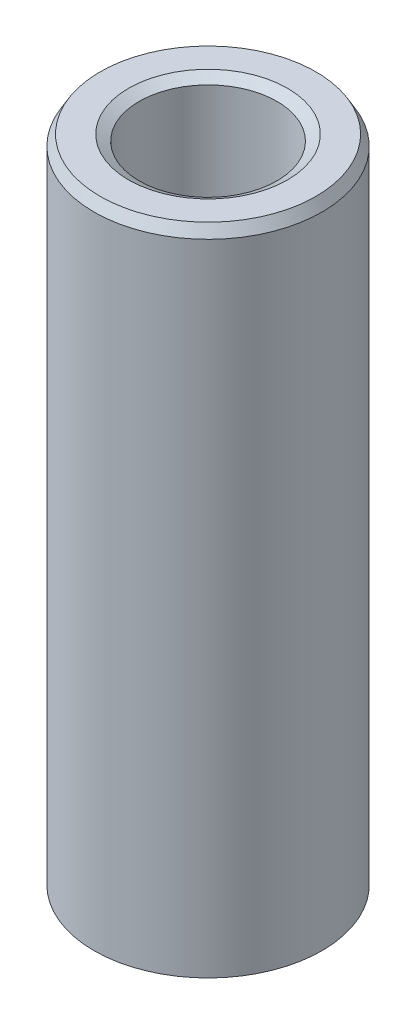
SolidWorks part; units mm, degrees
ref_plane "Front Plane" through (0, 0, 0) normal (0, 0, 1) x (1, 0, 0)
ref_plane "Top Plane" through (0, 0, 0) normal (0, 1, 0) x (1, 0, 0)
ref_plane "Right Plane" through (0, 0, 0) normal (1, 0, 0) x (0, 0, -1)
sketch "Sketch1" plane through (0, 0, 0) normal (0, 1, 0) x (1, 0, 0)
  circle A0 centre (0, 0) radius 15
  dimension "SLEEVE_OD" = 30
extrude "Boss-Extrude1" add sketch "Sketch1" along normal blind 86.3656
sketch "Sketch2" plane through (0, 0, 0) normal (0, 1, 0) x (1, 0, 0)
  circle A0 centre (0, 0) radius 9.0669
  dimension "BORE_D" = 18.1337
extrude "Cut-Extrude1" cut sketch "Sketch2" along normal through all
chamfer "Chamfer1" distance 1.3872 angle 30 4 edges at (0, 86.3656, 9.0669) (0, 0, 9.0669) (0, 0, 15) (0, 86.3656, 15) first distance on face at (0, 86.3656, 9.0669) first distance on face at (0, 0, 9.0669) first distance on face at (0, 86.3656, 15)
